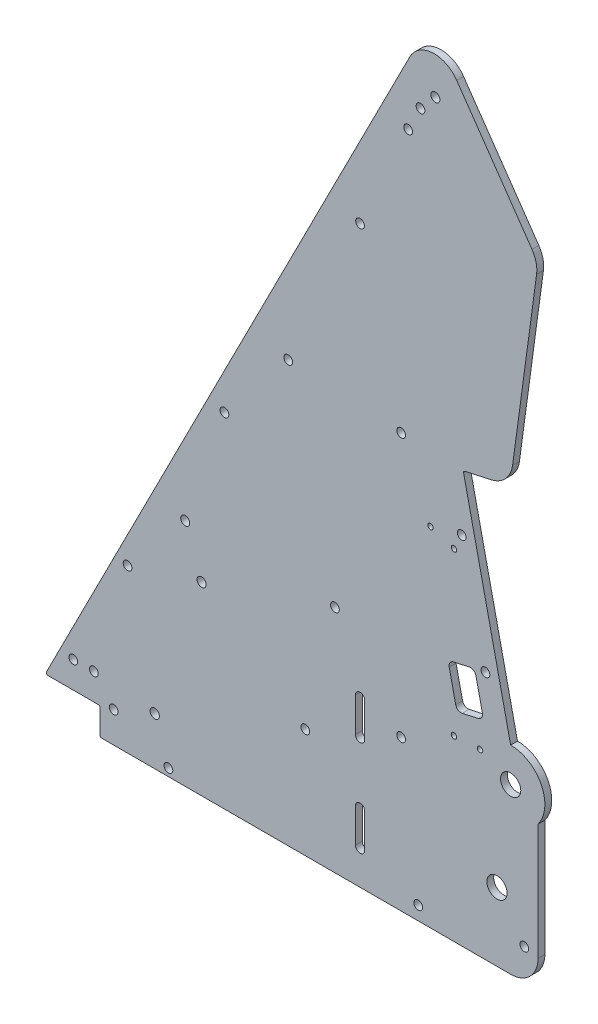
SolidWorks part; units mm, degrees
other "Markup1"
sketch "Sketch5"
ref_plane "Front Plane" through (0, 0, 0) normal (0, 0, 1) x (1, 0, 0)
ref_plane "Top Plane" through (0, 0, 0) normal (0, 1, 0) x (1, 0, 0)
ref_plane "Right Plane" through (0, 0, 0) normal (1, 0, 0) x (0, 0, -1)
sketch "Sketch1" plane through (0, 0, 0) normal (0, 0, 1) x (1, 0, 0)
  line L1 (228.6, -12.7) -> (228.6, 53.975)
  line L2 (178.7547, 351.4131) -> (0, 0)
  line L3 (228.6, 279.4) -> (178.7547, 351.4131)
  line L5 (0, 0) -> (25.4, 0)
  line L6 (25.4, 0) -> (25.4, -12.7)
  line L7 (25.4, -12.7) -> (228.6, -12.7)
  line L9 (215.9, 79.375) -> (193.9097, 178.5667)
  line L10 (193.9097, 178.5667) -> (215.6079, 183.377)
  line L11 (215.6079, 183.377) -> (228.6, 279.4)
  arc A0 (228.6, 53.975) -> (215.9, 79.375) centre (215.9, 63.5) ccw
  dimension "D7" = 12.7
  dimension "D8" = 76.2
  dimension "D10" = 31.75
  dimension "D2" = 292.1
  dimension "D3" = 25.4
  dimension "D4" = 215.9
  dimension "D5" = 394.2644
  dimension "D6" = 203.2
  dimension "D9" = 63.039
  dimension "D11" = 101.6
  dimension "D12" = 12.5
  dimension "D13" = 22.225
extrude "Boss-Extrude1" add sketch "Sketch1" along normal blind 3.175
sketch "Sketch2" plane through (0, 0, 3.175) normal (0, 0, 1) x (1, 0, 0)
  line L0 (178.7547, 351.4131) -> (0, 0) construction
  line L1 (25.4, -12.7) -> (228.6, -12.7) construction
  line L2 (215.9, 79.375) -> (193.9097, 178.5667) construction
  line L3 (193.9097, 178.5667) -> (215.6079, 183.377) construction
  line L4 (215.9, 79.375) -> (193.9097, 178.5667) construction
  line L5 (64.9432, 94.0578) -> (72.5445, 73.1732) construction
  line L6 (64.9432, 94.0578) -> (89.8317, 94.0578) construction
  line L10 (228.6, -12.7) -> (228.6, 53.975) construction
  circle A0 centre (64.9432, 94.0578) radius 2.0955
  circle A1 centre (180.975, 322.1643) radius 2.0955
  circle A2 centre (72.5445, 73.1732) radius 2.0955
  circle A3 centre (193.2078, 152.3944) radius 2.032
  circle A4 centre (215.9, 63.5) radius 4.699
  circle A7 centre (173.0375, -6.35) radius 2.032
  circle A8 centre (204.203, 102.7985) radius 2.032
  circle A26 centre (209.55, 19.05) radius 4.699
  arc A30 (228.6, 53.975) -> (215.9, 79.375) centre (215.9, 63.5) ccw construction
  circle A31 centre (165.1, 179.3875) radius 2.032
  dimension "D3" = 4.191
  dimension "D5" = 4.191
  dimension "D9" = 4.191
  dimension "D20" = 9.398
  dimension "D23" = 9.398
  dimension "D18" = 4.064
  dimension "D26" = 4.064
  dimension "D14" = 4.064
  dimension "D2" = 15.24
  dimension "D6" = 15.24
  dimension "D7" = 22.225
  dimension "D21" = 44.45
  dimension "D22" = 6.35
  dimension "D19" = 160.3375
  dimension "D24" = 44.45
  dimension "D25" = 6.35
  dimension "D27" = 25.4
  dimension "D28" = 50.8
  dimension "D29" = 6.35
  dimension "D17" = 6.35
  dimension "D33" = 55.5625
  dimension "D15" = 114.3
  dimension "D4" = 180.975
  dimension "D8" = 70
extrude "Cut-Extrude1" cut sketch "Sketch2" against normal through all
sketch "Sketch7" plane through (0, 0, 3.175) normal (0, 0, 1) x (1, 0, 0)
  line L0 (146.05, 3.175) -> (146.05, 19.05) construction
  line L1 (143.891, 3.175) -> (143.891, 19.05)
  line L2 (148.209, 3.175) -> (148.209, 19.05)
  line L3 (146.05, 47.625) -> (146.05, 63.5) construction
  line L4 (143.891, 47.625) -> (143.891, 63.5)
  line L5 (148.209, 47.625) -> (148.209, 63.5)
  line L6 (25.4, -12.7) -> (228.6, -12.7) construction
  line L12 (228.6, -12.7) -> (228.6, 53.975) construction
  line L13 (25.4, -12.7) -> (228.6, -12.7) construction
  arc A0 (143.891, 3.175) -> (148.209, 3.175) centre (146.05, 3.175) ccw
  arc A1 (148.209, 19.05) -> (143.891, 19.05) centre (146.05, 19.05) ccw
  arc A2 (143.891, 47.625) -> (148.209, 47.625) centre (146.05, 47.625) ccw
  arc A3 (148.209, 63.5) -> (143.891, 63.5) centre (146.05, 63.5) ccw
  circle A8 centre (50.8, 9.525) radius 2.159
  circle A10 centre (134.3935, 93.98) radius 2.032 construction
  circle A11 centre (134.3935, 93.98) radius 2.032
  point P2 (146.05, 11.1125)
  point P9 (146.05, 55.5625)
  point P20 (117.475, 25.2657)
  dimension "D1" = 4.318
  dimension "D5" = 4.318
  dimension "D2" = 15.875
  dimension "D3" = 15.875
  dimension "D4" = 44.45
  dimension "D6" = 95.25
  dimension "D7" = 82.55
  dimension "D8" = 15.875
  dimension "D9" = 22.225
extrude "Cut-Extrude2" cut sketch "Sketch7" against normal through all
sketch "Sketch10" plane through (0, 0, 3.175) normal (0, 0, 1) x (1, 0, 0)
  circle A1 centre (165.1, 57.15) radius 2.032
  circle A2 centre (120.65, 38.1) radius 2.032
  circle A3 centre (13.0465, 12.3347) radius 2.032
  circle A4 centre (22.5715, 12.3347) radius 2.032
  circle A5 centre (38.2114, 62.6398) radius 2.032
  dimension "D1" = 4.064
  dimension "D2" = 4.064
  dimension "D4" = 63.5
  dimension "D5" = 69.85
extrude "Cut-Extrude3" cut sketch "Sketch10" against normal up to next
fillet "Fillet1" radius 12.7 4 edges at (228.6, -12.7, 1.5875) (178.7547, 351.4131, 1.5875) (215.6079, 183.377, 1.5875) (228.6, 279.4, 1.5875)
fillet "Fillet2" radius 0.7937 4 edges at (25.4, -12.7, 1.5875) (25.4, 0, 1.5875) (193.9097, 178.5667, 1.5875) (0, 0, 1.5875)
sketch "Sketch12" plane through (0, 0, 3.175) normal (0, 0, 1) x (1, 0, 0)
  circle A0 centre (31.75, 1.5875) radius 2.032
  circle A1 centre (222.25, 1.5875) radius 2.032
  circle A2 centre (57.15, -9.2075) radius 2.032
  circle A3 centre (57.15, -9.2075) radius 2.286 construction
  dimension "D1" = 4.064
  dimension "D2" = 4.064
extrude "Cut-Extrude5" cut sketch "Sketch12" against normal through all
sketch "Sketch13" plane through (0, 0, 3.175) normal (0, 0, 1) x (1, 0, 0)
  line L2 (194.6847, 178.7385) -> (206.9592, 181.4597) construction
  line L5 (199.2434, 101.699) -> (189.6226, 145.0954) construction
  line L6 (189.6022, 69.9806) -> (201.7089, 70.5092) construction
  line L7 (186.8444, 98.9502) -> (199.2434, 101.699)
  line L8 (186.8444, 98.9502) -> (190.9676, 80.3518)
  line L9 (190.9676, 80.3518) -> (203.3665, 83.1006)
  line L10 (199.2434, 101.699) -> (203.3665, 83.1006)
  line L11 (189.6022, 69.9806) -> (190.9676, 80.3518) construction
  line L12 (201.7089, 70.5092) -> (203.3665, 83.1006) construction
  line L13 (215.9, 79.375) -> (194.0815, 177.7917) construction
  line L14 (178.7216, 148.5324) -> (189.6226, 145.0954) construction
  circle A0 centre (189.6022, 69.9806) radius 1.27
  circle A1 centre (201.7089, 70.5092) radius 1.27
  circle A2 centre (178.7216, 148.5324) radius 1.27
  circle A3 centre (189.6226, 145.0954) radius 1.27
  dimension "D7" = 2.54
  dimension "D2" = 11.43
  dimension "D3" = 76.2
  dimension "D4" = 12.7
  dimension "D5" = 19.05
  dimension "D6" = 120
  dimension "D8" = 110
  dimension "D9" = 80
  dimension "D10" = 12.7
  dimension "D11" = 44.45
  dimension "D12" = 11.43
extrude "Cut-Extrude6" cut sketch "Sketch13" against normal through all both and the other way through all
sketch "Sketch14" plane through (0, 0, 3.175) normal (0, 0, 1) x (1, 0, 0)
  line L0 (26.1937, -12.7) -> (215.9, -12.7) construction
  line L1 (228.6, 0) -> (228.6, 53.975) construction
  circle A0 centre (146.05, 254) radius 2.032
  circle A1 centre (112.7125, 182.5625) radius 2.032
  dimension "D1" = 4.064
  dimension "D2" = 195.2625
  dimension "D3" = 115.8875
  dimension "D4" = 82.55
  dimension "D5" = 266.7
extrude "Cut-Extrude7" cut sketch "Sketch14" against normal up to next
sketch "Sketch15" plane through (0, 0, 3.175) normal (0, 0, 1) x (1, 0, 0)
  line L0 (169.1053, 332.4434) -> (0.5868, 1.1536) construction
  circle A0 centre (83.1368, 146.6315) radius 2.032
  circle A1 centre (174.0995, 314.25) radius 2.032
  circle A2 centre (168.3414, 302.9303) radius 2.032
  circle A3 centre (174.0995, 314.25) radius 1.905 construction
  circle A4 centre (168.3414, 302.9303) radius 1.905 construction
  dimension "D1" = 4.064
  dimension "D4" = 4.064
  dimension "D2" = 7.62
  dimension "D3" = 82.55
extrude "Cut-Extrude8" cut sketch "Sketch15" against normal through all
fillet "Fillet3" radius 2.54 4 edges at (199.2434, 101.699, 1.5875) (186.8444, 98.9502, 1.5875) (190.9676, 80.3518, 1.5875) (203.3665, 83.1006, 1.5875)
equation "\"D6@Sketch2\"=\"D2@Sketch2\""
